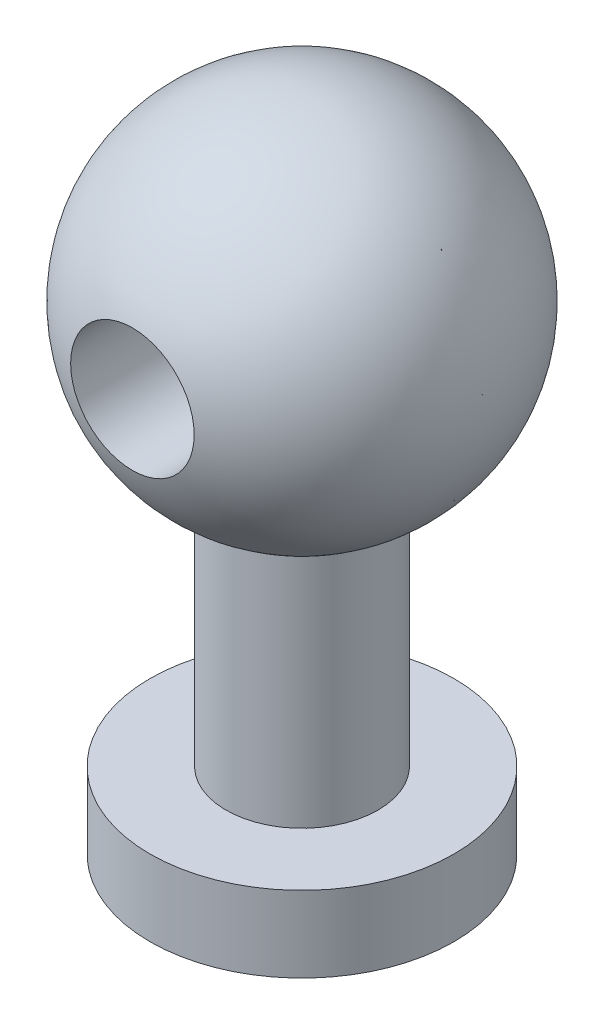
SolidWorks part; units mm, degrees
material "Plain Carbon Steel"
ref_plane "Front Plane" through (0, 0, 0) normal (0, 0, 1) x (1, 0, 0)
ref_plane "Top Plane" through (0, 0, 0) normal (0, 1, 0) x (1, 0, 0)
ref_plane "Right Plane" through (0, 0, 0) normal (1, 0, 0) x (0, 0, -1)
sketch "Sketch1" plane through (0, 0, 0) normal (0, 0, 1) x (1, 0, 0)
  line L0 (0, 0) -> (0, 34.7) construction
  line L1 (0, 0) -> (8, 0)
  line L2 (8, 0) -> (8, 4)
  line L3 (8, 4) -> (4, 4)
  line L4 (4, 4) -> (4, 16.5832)
  line L5 (0, 34.7) -> (0, 0)
  arc A0 (4, 16.5832) -> (0, 34.7) centre (0, 25.2) ccw
revolve "Revolve1" add sketch "Sketch1" angle 360 about L0
sketch "Sketch2" plane through (0, 0, 0) normal (0, 0, 1) x (1, 0, 0)
  circle A0 centre (0, 25.2) radius 3.25
  dimension "D1" = 6.5
extrude "Cut-Extrude1" cut sketch "Sketch2" against normal mid plane 40
